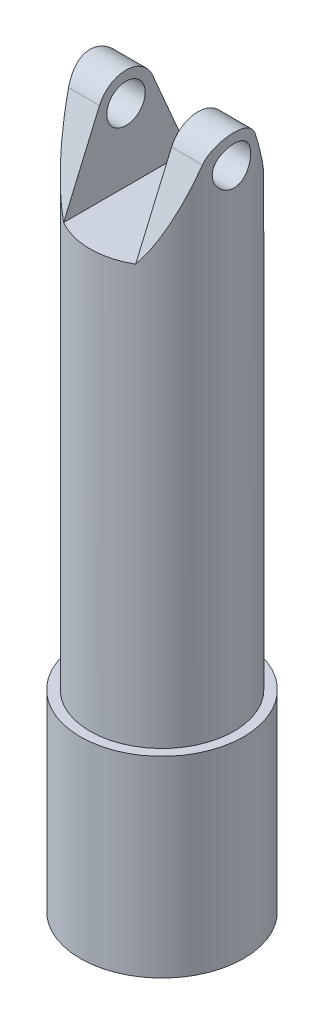
SolidWorks part; units mm, degrees
ref_plane "前视基准面" through (0, 0, 0) normal (0, 0, 1) x (1, 0, 0)
ref_plane "上视基准面" through (0, 0, 0) normal (0, 1, 0) x (1, 0, 0)
ref_plane "右视基准面" through (0, 0, 0) normal (1, 0, 0) x (0, 0, -1)
other "Configuration Table"
sketch "草图1" plane through (0, 0, 0) normal (0, 1, 0) x (1, 0, 0)
  circle A0 centre (0, 0) radius 17
extrude "凸台-拉伸1" add sketch "草图1" along normal blind 40
sketch "草图2" plane through (0, 40, 0) normal (0, 1, 0) x (1, 0, 0)
  circle A0 centre (0, 0) radius 15
extrude "凸台-拉伸2" add sketch "草图2" along normal blind 110
sketch "草图3" plane through (0, 0, 0) normal (0, 0, 1) x (1, 0, 0)
  line L0 (15, 150) -> (-15, 150) construction
  line L1 (-7.5, 173) -> (7.5, 173)
  line L2 (-7.5, 173) -> (-7.5, 127)
  line L3 (-7.5, 127) -> (7.5, 127)
  line L4 (7.5, 173) -> (7.5, 127)
  line L5 (0, 127) -> (0, 173) construction
  line L6 (-7.5, 150) -> (7.5, 150) construction
  point P0 (0, 150)
extrude "切除-拉伸1" cut sketch "草图3" against normal mid plane 30
sketch "草图4" plane through (0, 0, 0) normal (1, 0, 0) x (0, 0, -1)
  line L0 (0, 150) -> (0, 142) construction
  line L1 (12.9904, 150) -> (-12.9904, 150) construction
  circle A0 centre (0, 142) radius 4
extrude "切除-拉伸2" cut sketch "草图4" against normal mid plane 30 contours A0
sketch "草图5" plane through (0, 0, 0) normal (1, 0, 0) x (0, 0, -1)
  line L0 (0, 150) -> (0, 146) construction
  line L1 (12.9904, 150) -> (-12.9904, 150) construction
  line L10 (0, 146) -> (0, 142) construction
  circle A0 centre (0, 142) radius 4 construction
sketch "草图8" plane through (0, 0, 0) normal (1, 0, 0) x (0, 0, -1)
  line L0 (-12.9904, 127) -> (-5.511, 144.3726)
  line L1 (12.9904, 127) -> (5.511, 144.3726)
  line L2 (-12.9904, 127) -> (-12.9904, 150)
  line L3 (12.9904, 150) -> (-12.9904, 150) construction
  line L4 (-12.9904, 150) -> (-12.9904, 127) construction
  line L5 (-12.9904, 150) -> (12.9904, 150)
  line L6 (12.9904, 150) -> (12.9904, 127)
  arc A0 (5.511, 144.3726) -> (-5.511, 144.3726) centre (0, 142) ccw
  point P1 (0, 0)
  point P18 (0, 0)
extrude "切除-拉伸4" cut sketch "草图8" against normal mid plane 30
